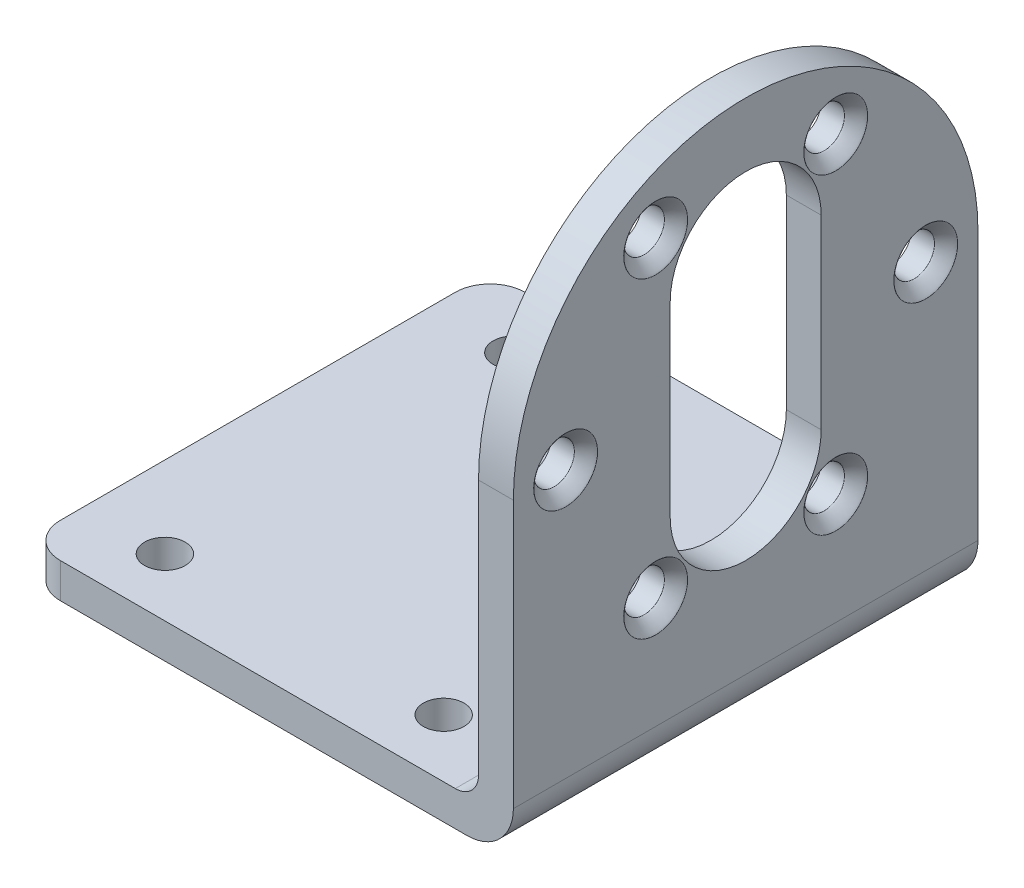
SolidWorks part; units mm, degrees
ref_plane "前视基准面" through (0, 0, 0) normal (0, 0, 1) x (1, 0, 0)
ref_plane "上视基准面" through (0, 0, 0) normal (0, 1, 0) x (1, 0, 0)
ref_plane "右视基准面" through (0, 0, 0) normal (1, 0, 0) x (0, 0, -1)
other "Configuration Table"
sketch "草图2" plane through (0, 0, 0) normal (1, 0, 0) x (0, 0, -1)
  line L0 (0, 0) -> (-15.5, 0) construction
  line L1 (0, -8) -> (0, 8) construction
  line L2 (-6.5, -8) -> (-6.5, 8)
  line L3 (6.5, -8) -> (6.5, 8)
  line L5 (-20, 0) -> (-20, -27)
  line L6 (20, 0) -> (20, -27)
  line L7 (-20, -27) -> (20, -27)
  circle A0 centre (0, 0) radius 20
  circle A1 centre (-15.5, 0) radius 1.75
  circle A2 centre (-7.75, 13.4234) radius 1.75
  circle A3 centre (7.75, 13.4234) radius 1.75
  circle A4 centre (15.5, 0) radius 1.75
  circle A5 centre (7.75, -13.4234) radius 1.75
  circle A6 centre (-7.75, -13.4234) radius 1.75
  arc A7 (-6.5, -8) -> (6.5, -8) centre (0, -8) ccw
  arc A8 (6.5, 8) -> (-6.5, 8) centre (0, 8) ccw
  arc A9 (-20, 0) -> (20, 0) centre (0, 0) ccw
  point P4 (0, 0)
  dimension "D1" = 40
  dimension "D2" = 3.5
  dimension "D7" = 15.5
  dimension "D9" = 8
  dimension "D3" = 0
  dimension "D4" = 15.5
  dimension "D6" = 15.5
  dimension "D8" = 13
  dimension "D10" = 27
  dimension "D5" = 6
extrude "凸台-拉伸1" add sketch "草图2" against normal blind 3 contours A0 A8 L3 A7 L2 A6 A5 A4 A3 A2 A1 | A0 L5 L7 L6 region at (0, -20.4717, 0) region at (0, 19.4343, 0)
sketch "草图3" plane through (0, -27, 0) normal (0, -1, 0) x (1, 0, 0)
  line L0 (0, 20) -> (0, -20)
  line L1 (0, 20) -> (-42, 20)
  line L2 (0, -20) -> (-42, -20)
  line L3 (-42, 20) -> (-42, -20)
  circle A0 centre (-11, 15) radius 1.75
  circle A1 centre (-11, -15) radius 1.75
  circle A2 centre (-35, 15) radius 1.75
  circle A3 centre (-35, -15) radius 1.75
  point P14 (0, 0)
  point P15 (0, 0)
  point P16 (0, 0)
  point P18 (-10.1437, 5.4581)
  point P20 (5.4462, -6.5237)
  dimension "D2" = 3.5
  dimension "D3" = 3.5
  dimension "D4" = 3.5
  dimension "D5" = 3.5
  dimension "D1" = 42
  dimension "D6" = 24
  dimension "D7" = 0
  dimension "D8" = 30
  dimension "D9" = 0
  dimension "D10" = 0
  dimension "D11" = 0
  dimension "D12" = 11
  dimension "D13" = 15
extrude "凸台-拉伸2" add sketch "草图3" against normal blind 3
fillet "圆角1" radius 3 1 edges at (-42, -25.5, 20)
fillet "圆角2" radius 3 1 edges at (-42, -25.5, -20)
fillet "圆角3" radius 2 1 edges at (-3, -24, 0)
fillet "圆角4" radius 4 1 edges at (0, -27, 0)
fillet "圆角5" radius 1 1 edges at (0, 13.4234, 6) conic radius 10
fillet "圆角6" radius 1 1 edges at (0, 13.4234, -9.5) conic radius 10
fillet "圆角7" radius 1 1 edges at (0, 0, 13.75) conic radius 10
fillet "圆角8" radius 1 1 edges at (0, 0, -17.25) conic radius 10
fillet "圆角9" radius 1 1 edges at (0, -13.4234, 6) conic radius 10
fillet "圆角10" radius 1 1 edges at (0, -13.4234, -9.5) conic radius 10
